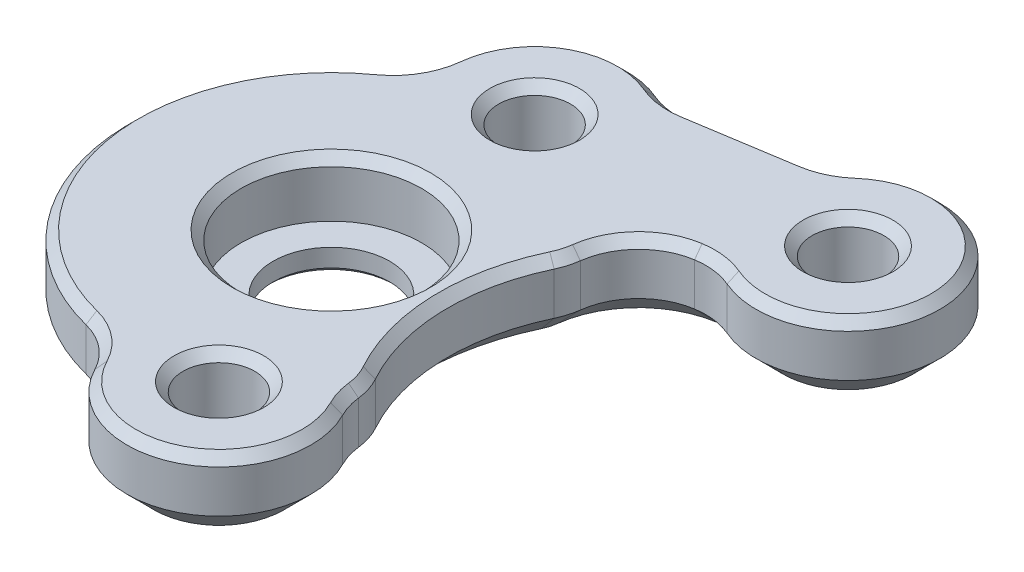
SolidWorks part; units mm, degrees
ref_plane "Front Plane" through (0, 0, 0) normal (0, 0, 1) x (1, 0, 0)
ref_plane "Top Plane" through (0, 0, 0) normal (0, 1, 0) x (1, 0, 0)
ref_plane "Right Plane" through (0, 0, 0) normal (1, 0, 0) x (0, 0, -1)
sketch "Sketch1" plane through (0, 0, 0) normal (0, 1, 0) x (1, 0, 0)
  circle A0 centre (0, 0) radius 9
  circle A1 centre (0, 0) radius 4.025
  dimension "D1" = 18
  dimension "D2" = 8.05
extrude "Boss-Extrude1" add sketch "Sketch1" along normal blind 3.5
sketch "Sketch2" plane through (0, 3.5, 0) normal (0, 1, 0) x (1, 0, 0)
  circle A0 centre (3.3433, -8.356) radius 1.6
  circle A1 centre (0.0612, 8.9998) radius 1.6
  circle A2 centre (3.3433, -8.356) radius 4.1
  circle A3 centre (0.0612, 8.9998) radius 4.1
  dimension "D1" = 2.5
extrude "Boss-Extrude2" add sketch "Sketch2" against normal blind 3.5
sketch "Sketch6" plane through (0, 0, 0) normal (0, -1, 0) x (-1, 0, 0)
  circle A0 centre (-14.2, 0) radius 9
  dimension "D1" = 18
  dimension "D2" = 14.2
extrude "Cut-Extrude2" cut sketch "Sketch6" against normal through all
sketch "Sketch3" plane through (0, 0, 0) normal (0, -1, 0) x (-1, 0, 0)
  circle A0 centre (-0.0612, 8.9998) radius 1.6
  arc A1 (-4.7701, -7.6319) -> (-1.8108, -8.8159) centre (0, 0) ccw construction
  arc A2 (1.5334, 8.8684) -> (-1.6538, 8.8467) centre (0, 0) ccw construction
  circle A4 centre (-3.3433, -8.356) radius 1.6
extrude "Cut-Extrude1" cut sketch "Sketch3" against normal blind 3.5
sketch "Sketch4" plane through (0, 0, 0) normal (0, -1, 0) x (-1, 0, 0)
  line L0 (-0.0612, 8.9998) -> (-12.1263, 10.9048) construction
  line L1 (-2.3537, 12.3989) -> (-8.898, 13.4322)
  line L3 (-5.8131, 6.8708) -> (-9.8338, 7.5057)
  circle A0 centre (-12.1263, 10.9048) radius 1.6
  arc A1 (-8.898, 13.4322) -> (-9.8338, 7.5057) centre (-12.1263, 10.9048) ccw
  arc A2 (-2.3537, 12.3989) -> (-4.047, 8.0388) centre (-0.0612, 8.9998) ccw
  arc A3 (-4.047, 8.0388) -> (-5.8131, 6.8708) centre (0, 0) ccw
  circle A5 centre (-12.1263, 10.9048) radius 4.1 construction
  point P4 (-12.1263, 10.9048)
  point P5 (-12.1263, 10.9048)
  point P8 (-7.2556, 11.7052)
  point P9 (-12.1263, 10.9048)
  point P10 (-8.0263, 10.9048)
  point P13 (-8.0263, 10.9048)
  point P17 (-8.0263, 10.9048)
  dimension "D2" = 3
  dimension "D1" = 2.5
extrude "Boss-Extrude3" add sketch "Sketch4" against normal blind 3.5
sketch "Sketch5" plane through (0, 0, 0) normal (0, -1, 0) x (-1, 0, 0)
  circle A0 centre (0, 0) radius 4.025
  circle A1 centre (0, 0) radius 2.6
  dimension "D1" = 5.2
extrude "Boss-Extrude4" add sketch "Sketch5" against normal blind 1
fillet "Fillet1" radius 3 7 edges at (-3.9373, 1.75, -8.0931) (-0.7102, 1.75, 8.9719) (9.8338, 1.75, -7.5057) (8.898, 1.75, -13.4322) (2.3537, 1.75, -12.3989) (7.1, 1.75, -5.5308) (7.1, 1.75, 5.5308)
fillet "Fillet9" radius 3 2 edges at (5.8131, 1.75, -6.8708) (6.7029, 1.75, 6.0059)
chamfer "倒角1" distance 1.2 angle 45 16 edges at (16.1761, 0, -11.5442) (8.7151, 0, -13.5234) (9.6878, 0, -7.3626) (5.6259, 0, -12.9156) (8.8438, 0, -7.3493) (2.4996, 0, -12.542) (7.1582, 0, -6.4755) (-2.0077, 0, -12.5396) (6.238, 0, -4.3017) (-4.406, 0, -8.2391) (5.2046, 0, 0.2865) (-8.8433, 0, 1.6723) (6.5641, 0, 4.9054) (-1.0932, 0, 9.279) (6.7966, 0, 5.9989) (5.2201, 0, 12.0012)
chamfer "倒角2" distance 0.2 angle 45 4 edges at (3.3433, 0, 9.956) (12.1263, 0, -12.5048) (0, 0, -2.6) (0.0612, 0, -7.3998)
chamfer "倒角3" distance 0.4 angle 45 20 edges at (12.1263, 3.5, -12.5048) (0, 3.5, 4.025) (0.0612, 3.5, -7.3998) (3.3433, 3.5, 9.956) (6.5641, 3.5, 4.9054) (6.7966, 3.5, 5.9989) (5.2201, 3.5, 12.0012) (-1.0932, 3.5, 9.279) (-8.8433, 3.5, 1.6723) (-4.406, 3.5, -8.2391) (-2.0077, 3.5, -12.5396) (2.4996, 3.5, -12.542) (5.6259, 3.5, -12.9156) (8.7151, 3.5, -13.5234) (16.1761, 3.5, -11.5442) (9.6878, 3.5, -7.3626) (8.8438, 3.5, -7.3493) (7.1582, 3.5, -6.4755) (6.238, 3.5, -4.3017) (5.2046, 3.5, 0.2865)
equation "\"D2@Sketch6\"=5.2+\"D1@Sketch6\"/2"
